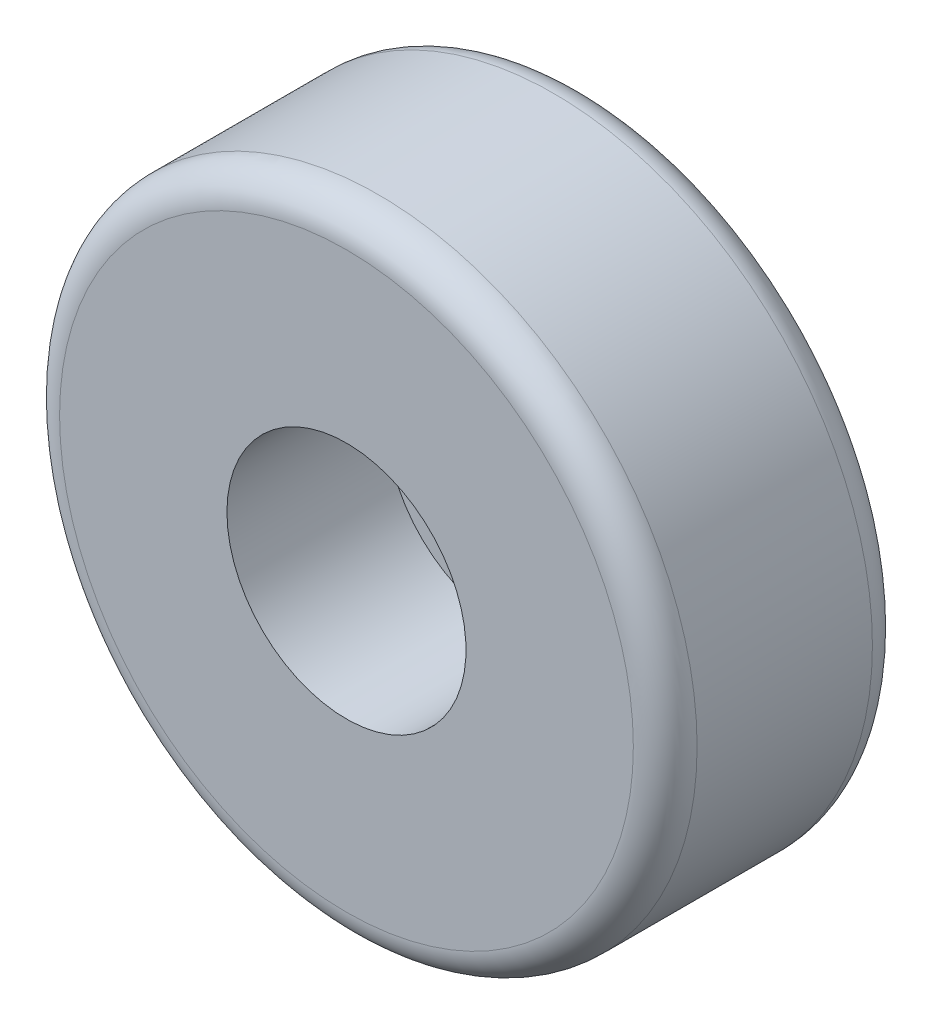
SolidWorks part; units mm, degrees
ref_plane "Front Plane" through (0, 0, 0) normal (0, 0, 1) x (1, 0, 0)
ref_plane "Top Plane" through (0, 0, 0) normal (0, 1, 0) x (1, 0, 0)
ref_plane "Right Plane" through (0, 0, 0) normal (1, 0, 0) x (0, 0, -1)
sketch "Sketch1" plane through (0, 0, 0) normal (0, 0, 1) x (1, 0, 0)
  circle A0 centre (0, 0) radius 101.6
  circle A1 centre (0, 0) radius 38.1
  circle A2 centre (0, 0) radius 76.2
  dimension "D1" = 203.2
  dimension "D2" = 76.2
  dimension "D3" = 152.4
extrude "Boss-Extrude7" add sketch "Sketch1" along normal blind 76.2 contours A1 | A1 | A1 | A1 | A1 | A0 A2 region at (-98.7263, 0, 0) region at (-74.0447, 0, 0)
extrude "Boss-Extrude9" add sketch "Sketch1<11>" along normal blind 25.4 contours A1 region at (0, 0, 0)
sketch "Sketch1<11>" plane through (0, 0, 0) normal (0, 0, 1) x (1, 0, 0) same geometry as "Sketch1"
fillet "Fillet1" radius 10.16 2 edges at (101.6, 0, 76.2) (101.6, 0, 0)
sketch "Sketch2" plane through (0, 0, 0) normal (0, 0, -1) x (-1, 0, 0)
  circle A0 centre (0, 0) radius 74.8205
  circle A1 centre (0, 0) radius 38.1
  dimension "D1" = 76.2
extrude "Cut-Extrude1" cut sketch "Sketch2" against normal blind 12.7
